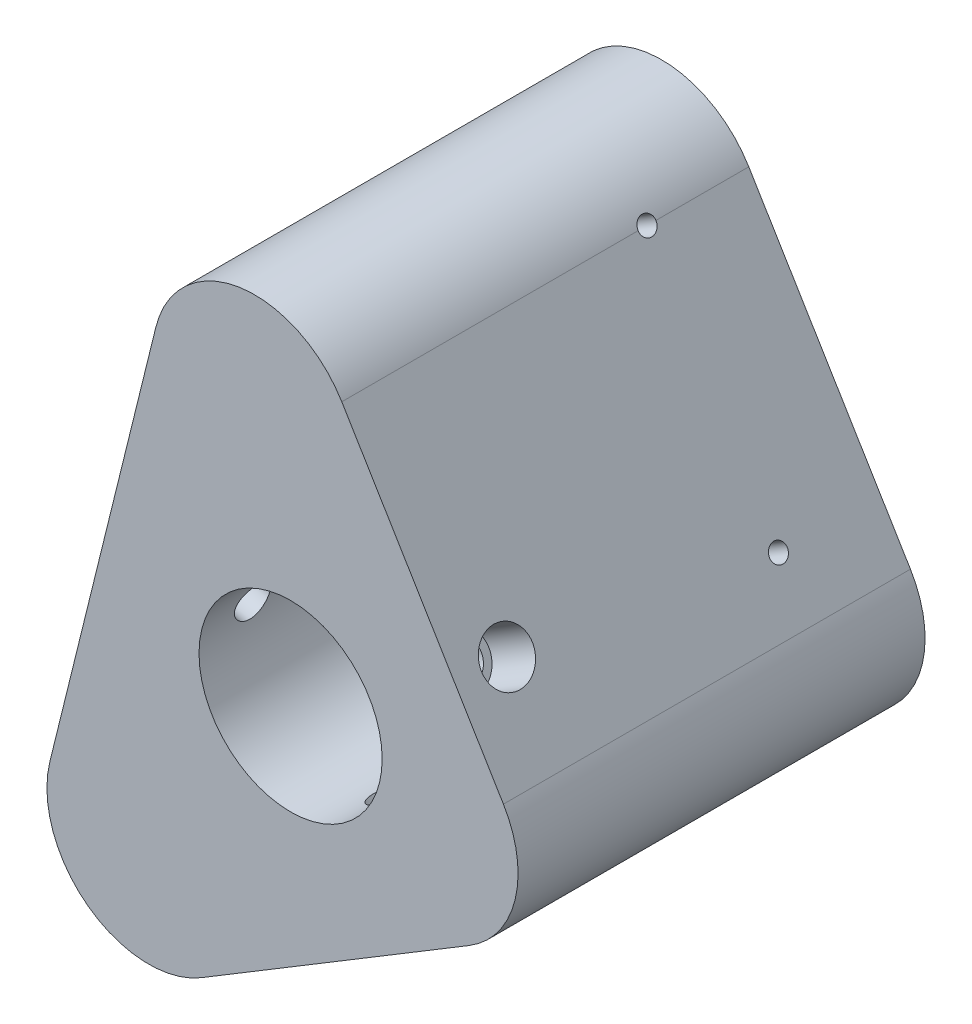
SolidWorks part; units mm, degrees
ref_plane "Front Plane" through (0, 0, 0) normal (0, 0, 1) x (1, 0, 0)
ref_plane "Top Plane" through (0, 0, 0) normal (0, 1, 0) x (1, 0, 0)
ref_plane "Right Plane" through (0, 0, 0) normal (1, 0, 0) x (0, 0, -1)
sketch "Sketch1" plane through (0, 0, 0) normal (0, 0, 1) x (1, 0, 0)
  line L0 (-13.9462, -18.9369) -> (-3.5289, 23.2519) construction
  line L1 (-3.5289, 23.2519) -> (12.3568, -3.0512) construction
  line L2 (12.3568, -3.0512) -> (-13.9462, -18.9369) construction
  line L3 (-23.6546, -16.5397) -> (-13.2373, 25.6491)
  line L4 (5.031, 28.4217) -> (20.9168, 2.1186)
  line L5 (17.5266, -11.6111) -> (-8.7764, -27.4969)
  line L6 (26.0866, -6.4413) -> (-29.442, -39.9779) construction
  line L7 (-29.442, -39.9779) -> (-7.45, 49.0873) construction
  line L8 (-7.45, 49.0873) -> (26.0866, -6.4413) construction
  circle A0 centre (0, 0) radius 9
  arc A3 (-23.6546, -16.5397) -> (-8.7764, -27.4969) centre (-13.9462, -18.9369) ccw
  arc A4 (5.031, 28.4217) -> (-13.2373, 25.6491) centre (-3.5289, 23.2519) ccw
  arc A5 (17.5266, -11.6111) -> (20.9168, 2.1186) centre (12.3568, -3.0512) ccw
  dimension "D1" = 18
  dimension "D2" = 45
  dimension "D3" = 45
  dimension "D4" = 10
extrude "Boss-Extrude1" add sketch "Sketch1" along normal blind 70
sketch "Sketch2" plane through (9.8226, -16.2639, 0) normal (0.517, -0.856, 0) x (0.856, 0.517, 0)
  line L0 (-21.7279, 70) -> (9, 70) construction
  circle A0 centre (0, 65) radius 2.5
  dimension "D1" = 5
  dimension "D2" = 5
extrude "Cut-Extrude1" cut sketch "Sketch2" against normal blind 5
sketch "Sketch3" plane through (7.2377, -11.984, 0) normal (0.517, -0.856, 0) x (0.856, 0.517, 0)
  circle A0 centre (0, 65) radius 1.75
  dimension "D1" = 3.5
extrude "Cut-Extrude2" cut sketch "Sketch3" against normal up to surface (5.1718 mm away) up to face at (9, 0, 70)
pattern_circular "CirPattern1" count 2 every 90 about axis through (0, 0, 0) along (0, 0, 1) of "Cut-Extrude1", "Cut-Extrude2"
sketch "Sketch5" plane through (0, 0, 0) normal (0, 1, 0) x (1, 0, 0)
  line L0 (-24.5682, 0) -> (0, 0) construction
  line L2 (-24.5682, -30) -> (0, -30)
  line L3 (-24.5682, -5) -> (0, -5)
  line L4 (0, 0) -> (0, -30) construction
  line L6 (-24.5682, -30) -> (-24.5682, -5)
  line L7 (0, -30) -> (0, -5)
  dimension "D1" = 5
  dimension "D2" = 25
revolve "Cut-Revolve1" cut sketch "Sketch5" angle 360 about L4
sketch "Sketch6" plane through (0, 0, 0) normal (0, 0, -1) x (-1, 0, 0)
  circle A0 centre (0, 0) radius 9
extrude "Boss-Extrude2" add sketch "Sketch6" against normal up to surface (5 mm away) up to face at (9, 0, 5)
sketch "Sketch8" plane through (0, 0, 30) normal (0, 0, -1) x (-1, 0, 0)
  circle A0 centre (0, 0) radius 9 construction
  circle A1 centre (0, 0) radius 9
extrude "Boss-Extrude3" add sketch "Sketch8" against normal blind 3
sketch "Sketch9" plane through (0, 0, 0) normal (0, 0, -1) x (-1, 0, 0)
  circle A0 centre (0, 0) radius 8 construction
  circle A1 centre (0, 8) radius 1.875
  circle A2 centre (8, 0) radius 1.875
  circle A3 centre (0, -8) radius 1.875
  circle A4 centre (-8, 0) radius 1.875
  point P14 (0, 0)
  dimension "D1" = 16
  dimension "D2" = 3.75
  dimension "D3" = 4
extrude "Cut-Extrude3" cut sketch "Sketch9" against normal up to surface (5 mm away) up to face at (1.1561, -0.2855, 5)
sketch "Sketch10" plane through (0, 0, 30) normal (0, 0, -1) x (-1, 0, 0)
  line L1 (13.2373, 25.6491) -> (23.6546, -16.5397) construction
  line L2 (8.7764, -27.4969) -> (-17.5266, -11.6111) construction
  line L3 (-20.9168, 2.1186) -> (-5.031, 28.4217) construction
  line L4 (13.2373, 25.6491) -> (23.6546, -16.5397)
  line L5 (8.7764, -27.4969) -> (-17.5266, -11.6111)
  line L6 (-20.9168, 2.1186) -> (-5.031, 28.4217)
  arc A0 (13.2373, 25.6491) -> (-5.031, 28.4217) centre (3.5289, 23.2519) ccw construction
  arc A1 (8.7764, -27.4969) -> (23.6546, -16.5397) centre (13.9462, -18.9369) ccw construction
  arc A2 (-20.9168, 2.1186) -> (-17.5266, -11.6111) centre (-12.3568, -3.0512) ccw construction
  arc A3 (13.2373, 25.6491) -> (-5.031, 28.4217) centre (3.5289, 23.2519) ccw
  arc A4 (8.7764, -27.4969) -> (23.6546, -16.5397) centre (13.9462, -18.9369) ccw
  arc A5 (-20.9168, 2.1186) -> (-17.5266, -11.6111) centre (-12.3568, -3.0512) ccw
sketch "Sketch11" plane through (0, 0, 0) normal (0, 0, -1) x (-1, 0, 0)
  circle A0 centre (0, 0) radius 4
  dimension "D1" = 8
extrude "Cut-Extrude4" cut sketch "Sketch11" against normal blind 3
sketch "Sketch12" plane through (0, 0, 0) normal (0, 1, 0) x (1, 0, 0)
  line L0 (-30.7423, -30) -> (34.4283, -30)
  line L1 (34.4283, -30) -> (34.4283, 3.2197)
  line L2 (34.4283, 3.2197) -> (-30.7423, 3.2197)
  line L3 (-30.7423, 3.2197) -> (-30.7423, -30)
extrude "Cut-Extrude5" cut sketch "Sketch12" against normal through all and the other way through all
sketch "Sketch13" plane through (-18.446, 4.5547, 0) normal (-0.9708, 0.2397, 0) x (0, 0, 1)
  line L4 (25.1827, 0) -> (50.8173, 0) construction
  line L8 (30, 21.7279) -> (30, -21.7279) construction
  circle A0 centre (38, 0) radius 5
  point P6 (30, 0)
  dimension "D1" = 10
  dimension "D2" = 8
extrude "Cut-Extrude6" cut sketch "Sketch13" against normal up to next
pattern_circular "CirPattern2" count 2 over 225 about axis through (0, 0, 70) along (0, 0, 1) of "Cut-Extrude1", "Cut-Extrude2"
ref_plane "Plane1" through (0, 0, 35) normal (0, 0, -1) x (-1, 0, 0)
sketch "Sketch14" plane through (0, 0, 35) normal (0, 0, -1) x (-1, 0, 0)
  line L0 (13.2373, 25.6491) -> (23.6546, -16.5397) construction
  line L1 (1.0316, 20.8512) -> (4.3593, 19.8888)
  line L2 (4.3593, 19.8888) -> (6.8567, 22.2895)
  line L3 (6.8567, 22.2895) -> (6.0262, 25.6526)
  line L4 (6.0262, 25.6526) -> (2.6985, 26.615)
  line L5 (2.6985, 26.615) -> (0.2012, 24.2142)
  line L6 (0.2012, 24.2142) -> (1.0316, 20.8512)
  line L7 (-14.8541, -5.4519) -> (-11.5264, -6.4142)
  line L8 (-11.5264, -6.4142) -> (-9.0291, -4.0135)
  line L9 (-9.0291, -4.0135) -> (-9.8595, -0.6504)
  line L10 (-9.8595, -0.6504) -> (-13.1872, 0.3119)
  line L11 (-13.1872, 0.3119) -> (-15.6845, -2.0888)
  line L12 (-15.6845, -2.0888) -> (-14.8541, -5.4519)
  line L13 (11.4489, -21.3376) -> (14.7766, -22.3)
  line L14 (14.7766, -22.3) -> (17.274, -19.8993)
  line L15 (17.274, -19.8993) -> (16.4435, -16.5362)
  line L16 (16.4435, -16.5362) -> (13.1158, -15.5738)
  line L17 (13.1158, -15.5738) -> (10.6185, -17.9745)
  line L18 (10.6185, -17.9745) -> (11.4489, -21.3376)
  circle A0 centre (3.5289, 23.2519) radius 3 construction
  circle A1 centre (-12.3568, -3.0512) radius 3 construction
  circle A2 centre (13.9462, -18.9369) radius 3 construction
  dimension "D1" = 6
  dimension "D2" = 6
  dimension "D3" = 6
extrude "Cut-Extrude7" cut sketch "Sketch14" against normal blind 3
sketch "Sketch15" plane through (0, 0, 30) normal (0, 0, -1) x (-1, 0, 0)
  circle A0 centre (3.5289, 23.2519) radius 1.75
  circle A1 centre (-12.3568, -3.0512) radius 1.75
  circle A2 centre (13.9462, -18.9369) radius 1.75
  dimension "D1" = 3.5
extrude "Cut-Extrude8" cut sketch "Sketch15" against normal blind 10
sketch "Sketch16" plane through (16.2639, 9.8226, 0) normal (0.856, 0.517, 0) x (0, 0, -1)
  line L2 (-70, -9) -> (-30, -9) construction
  line L3 (-70, 21.7279) -> (-30, 21.7279) construction
  circle A0 centre (-40, 21.7279) radius 0.875
  circle A1 centre (-40, -3.25) radius 0.875
  point P4 (0, 0)
  point P6 (-47.7199, 0)
  point P8 (-50, -19)
  point P10 (0, 0)
  dimension "D1" = 1.75
  dimension "D3" = 5.75
  dimension "D2" = 10
extrude "Cut-Extrude9" cut sketch "Sketch16" against normal blind 5
ref_plane "Plane3" through (2.1575, 8.7376, 0) normal (-0.2397, -0.9708, 0) x (-0.9708, 0.2397, 0)
ref_plane "Plane4" through (0, 0, 0) normal (-0.2397, -0.9708, 0) x (-0.9708, 0.2397, 0)
mirror "Mirror1" about plane through (0, 0, 0) normal (-0.2397, -0.9708, 0) of "Cut-Extrude9"
equation "\"fuse_diam\"= 0.07"
equation "\"fuse_rad\"= 0.035"
equation "\"battery_length\"= 0.076"
equation "\"battery_width\"= 0.034"
equation "\"battery_height\"= 0.051"
equation "\"bat_bay_length\"= 0.096"
equation "\"wing_shelf\"= 0.0175"
equation "\"shell\"= 0.002"
equation "\"chord_length\"= 0.09"
equation "\"tail_length\"= 0.26598000000000005"
equation "\"tail_diam\"= 0.035"
equation "\"connector\"= 0.06649500000000001"
